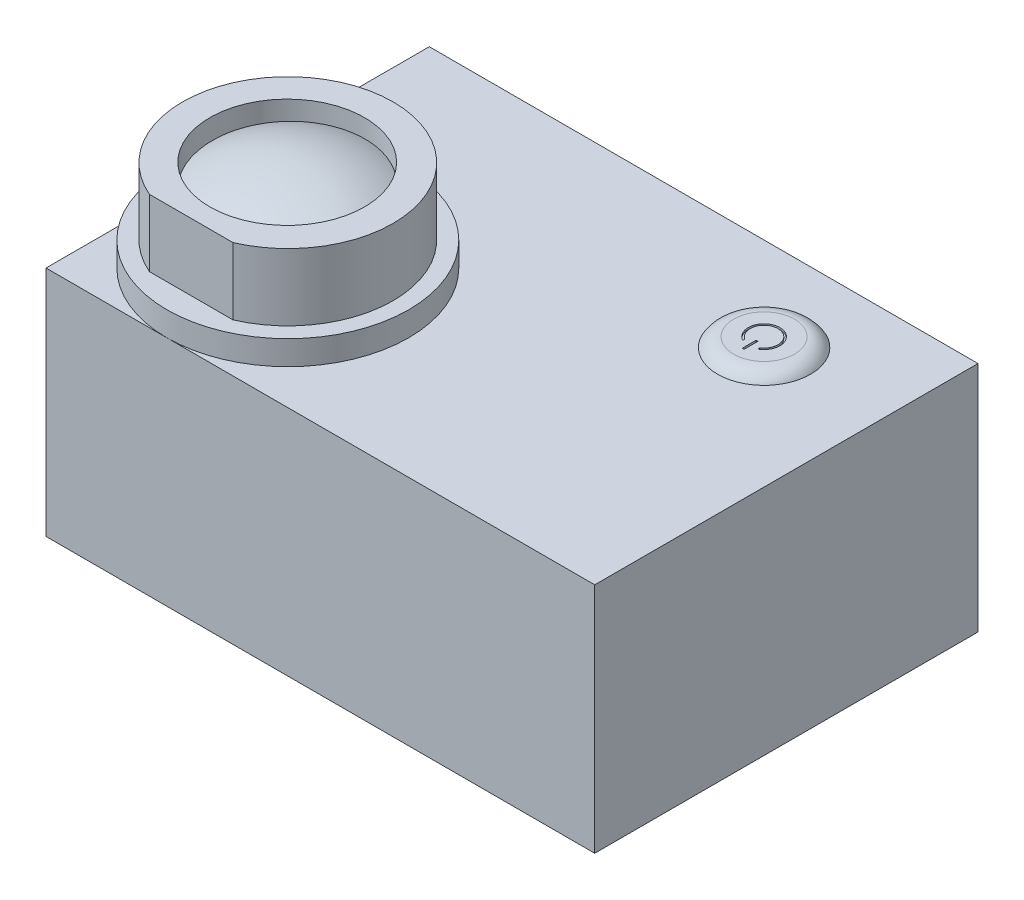
SolidWorks part; units mm, degrees
ref_plane "Alzado" through (0, 0, 0) normal (0, 0, 1) x (1, 0, 0)
ref_plane "Planta" through (0, 0, 0) normal (0, 1, 0) x (1, 0, 0)
ref_plane "Vista lateral" through (0, 0, 0) normal (1, 0, 0) x (0, 0, -1)
sketch "Croquis1" plane through (0, 0, 0) normal (0, 1, 0) x (1, 0, 0)
  line L1 (29.5, -20.605) -> (-29.5, -20.605)
  line L2 (29.5, -20.605) -> (29.5, 20.605)
  line L3 (29.5, 20.605) -> (-29.5, 20.605)
  line L4 (-29.5, -20.605) -> (-29.5, 20.605)
  line L5 (29.5, -20.605) -> (-29.5, 20.605) construction
  line L6 (29.5, 20.605) -> (-29.5, -20.605) construction
  point P0 (0, 0)
  dimension "D1" = 59
  dimension "D2" = 41.21
extrude "Saliente-Extruir1" add sketch "Croquis1" along normal blind 25
sketch "Croquis2" plane through (0, 25, 0) normal (0, 1, 0) x (1, 0, 0)
  line L0 (-29.5, 20.605) -> (-29.5, -20.605) construction
  line L1 (-29.5, -20.605) -> (29.5, -20.605) construction
  circle A0 centre (-16.5, -7.605) radius 13
  dimension "D1" = 26
extrude "Saliente-Extruir2" add sketch "Croquis2" along normal blind 9.81
sketch "Croquis4" plane through (0, 34.81, 0) normal (0, 1, 0) x (1, 0, 0)
  circle A0 centre (-16.5, -7.605) radius 11.32
  circle A1 centre (-16.5, -7.605) radius 13
extrude "Cortar-Extruir1" cut sketch "Croquis4" against normal blind 7.2
sketch "Croquis6" plane through (0, 34.81, 0) normal (0, 1, 0) x (1, 0, 0)
  line L1 (-12.0066, -17.995) -> (-20.9934, -17.995)
  arc A0 (-20.9934, -17.995) -> (-12.0066, -17.995) centre (-16.5, -7.605) ccw
  point P6 (-16.5, -17.995)
extrude "Cortar-Extruir2" cut sketch "Croquis6" against normal blind 7.2
sketch "Croquis7" plane through (0, 34.81, 0) normal (0, 1, 0) x (1, 0, 0)
  circle A0 centre (-16.5686, -7.6006) radius 8.32
extrude "Cortar-Extruir3" cut sketch "Croquis7" against normal blind 5
ref_plane "Plano1" through (-16.5, 0, 0) normal (-1, 0, 0) x (0, 0, 1)
sketch "Croquis9" plane through (-16.5, 0, 0) normal (-1, 0, 0) x (0, 0, 1)
  line L0 (15.9206, 32.31) -> (7.14, 32.31)
  line L1 (15.9206, 29.81) -> (15.9206, 34.81) construction
  line L2 (7.14, 32.31) -> (7.14, 34.81)
  line L3 (17.995, 34.81) -> (-3.715, 34.81) construction
  arc A0 (7.14, 34.81) -> (15.9206, 32.31) centre (7.14, 18.1403) cw
revolve "Revolución2" add sketch "Croquis9" angle 360 about L2
sketch "Croquis10" plane through (0, 25, 0) normal (0, 1, 0) x (1, 0, 0)
  circle A0 centre (16.5, 10.605) radius 5
extrude "Saliente-Extruir3" add sketch "Croquis10" along normal blind 1
fillet "Redondeo1" radius 2 1 edges at (16.5, 26, -5.605)
sketch "Croquis12" plane through (0, 26, 0) normal (0, 1, 0) x (1, 0, 0)
  line L0 (16.5, 10.605) -> (16.5, 9.855) construction
  line L1 (15.6938, 9.1945) -> (15.6938, 9.313)
  line L2 (16.55, 8.355) -> (16.45, 8.355)
  line L3 (16.6, 8.405) -> (16.6, 9.805)
  line L4 (16.55, 9.855) -> (16.45, 9.855)
  line L5 (16.4, 8.405) -> (16.4, 9.805)
  line L6 (17.3062, 9.1945) -> (17.3062, 9.313)
  arc A0 (17.3286, 9.3546) -> (15.6714, 9.3546) centre (16.5, 10.605) ccw
  arc A1 (17.3822, 9.1518) -> (15.6178, 9.1518) centre (16.5, 10.605) ccw
  arc A2 (15.6938, 9.1945) -> (15.6178, 9.1518) centre (15.6438, 9.1945) cw
  arc A3 (15.6714, 9.3546) -> (15.6938, 9.313) centre (15.6438, 9.313) cw
  arc A4 (17.3062, 9.1945) -> (17.3822, 9.1518) centre (17.3562, 9.1945) ccw
  arc A5 (17.3062, 9.313) -> (17.3286, 9.3546) centre (17.3562, 9.313) cw
  arc A6 (16.6, 8.405) -> (16.55, 8.355) centre (16.55, 8.405) cw
  arc A7 (16.4, 8.405) -> (16.45, 8.355) centre (16.45, 8.405) ccw
  arc A8 (16.55, 9.855) -> (16.6, 9.805) centre (16.55, 9.805) cw
  arc A9 (16.45, 9.855) -> (16.4, 9.805) centre (16.45, 9.805) ccw
  point P12 (15.6938, 9.1083)
  point P16 (15.6938, 9.3401)
  point P19 (17.3062, 9.1083)
  point P22 (17.3062, 9.3401)
  dimension "D1" = 0.05
  dimension "D2" = 0.05
  dimension "D3" = 0.05
extrude "Cortar-Extruir5" cut sketch "Croquis12" against normal blind 0.2
sketch "Croquis13" plane through (0, 0, -20.605) normal (0, 0, -1) x (-1, 0, 0)
  circle A0 centre (19, 13.3) radius 2.5
extrude "Cortar-Extruir6" cut sketch "Croquis13" against normal blind 5.2
thread "Rosca1" pitch 0.8 method extrude profile "Perfil de rosca1" start angle 0, offset 0, length 0, pitch 0.8, diameter 5
ref_plane "Plano2" through (-16.5, 13.3, -20.605) normal (0, -1, 0) x (1, 0, 0)
sketch "Perfil de rosca1" plane through (-16.5, 13.3, -20.605) normal (0, -1, 0) x (1, 0, 0)
  line L0 (0, 0) -> (0, 0.8) construction
  line L11 (0, 0) -> (0, 0.7)
  line L12 (0, 0.7) -> (-0.433, 0.45)
  line L13 (-0.433, 0.45) -> (-0.433, 0.25)
  line L15 (-0.433, 0.25) -> (0, 0)
  line L17 (-0.433, 0.35) -> (0, 0.35) construction
  point P2 (0, 0)
  dimension "Pitch" = 0.8
  dimension "Profile_Angle" = 60
  dimension "Profile_Land" = 0.2
  dimension "Profile_Height" = 0.433
sketch "Croquis16" plane through (-29.5, 0, 0) normal (-1, 0, 0) x (0, 0, 1)
  line L1 (-20.605, 25) -> (-20.605, 0) construction
  line L2 (-2.92, 17.66) -> (1.43, 17.66)
  line L4 (-2.3921, 20.4) -> (0.9021, 20.4)
  line L5 (1.93, 18.16) -> (1.93, 19.16)
  line L6 (1.93, 19.16) -> (1.3307, 20.1575)
  line L7 (-3.42, 18.16) -> (-3.42, 19.16)
  line L8 (-3.42, 19.16) -> (-2.8207, 20.1575)
  line L9 (-20.605, 25) -> (-20.605, 16.4)
  line L10 (-13.905, 16.9) -> (-13.905, 19.16)
  line L11 (-13.405, 16.4) -> (-6.445, 16.4)
  line L12 (-2.1027, 7.92) -> (-7.3176, 7.92)
  line L13 (-12.5324, 20.4) -> (-7.3176, 20.4)
  line L14 (-5.945, 16.9) -> (-5.945, 19.16)
  line L15 (-5.945, 19.16) -> (-6.9517, 20.2408)
  line L16 (-13.905, 19.16) -> (-12.8983, 20.2408)
  line L23 (-1.2302, 11.92) -> (-8.1902, 11.92)
  line L24 (-8.6902, 11.42) -> (-8.6902, 9.16)
  line L25 (-8.6902, 9.16) -> (-7.6834, 8.0792)
  line L26 (-0.7302, 9.16) -> (-1.7369, 8.0792)
  line L27 (-0.7302, 11.42) -> (-0.7302, 9.16)
  arc A0 (-13.405, 16.4) -> (-13.905, 16.9) centre (-13.405, 16.9) cw
  arc A1 (-5.945, 16.9) -> (-6.445, 16.4) centre (-6.445, 16.9) cw
  arc A2 (-2.92, 17.66) -> (-3.42, 18.16) centre (-2.92, 18.16) cw
  arc A3 (1.93, 18.16) -> (1.43, 17.66) centre (1.43, 18.16) cw
  arc A4 (-12.8983, 20.2408) -> (-12.5324, 20.4) centre (-12.5324, 19.9) cw
  arc A5 (-6.9517, 20.2408) -> (-7.3176, 20.4) centre (-7.3176, 19.9) ccw
  arc A6 (-2.3921, 20.4) -> (-2.8207, 20.1575) centre (-2.3921, 19.9) ccw
  arc A7 (1.3307, 20.1575) -> (0.9021, 20.4) centre (0.9021, 19.9) ccw
  arc A9 (-7.3176, 7.92) -> (-7.6834, 8.0792) centre (-7.3176, 8.42) cw
  arc A12 (-1.2302, 11.92) -> (-0.7302, 11.42) centre (-1.2302, 11.42) cw
  arc A13 (-8.6902, 11.42) -> (-8.1902, 11.92) centre (-8.1902, 11.42) cw
  arc A14 (-1.7369, 8.0792) -> (-2.1027, 7.92) centre (-2.1027, 8.42) cw
  point P22 (-13.905, 16.4)
  point P25 (-5.945, 16.4)
  point P61 (-7.3176, 7.92)
  dimension "D1" = 0.5
  dimension "D2" = 0.5
extrude "Cortar-Extruir8" cut sketch "Croquis16" against normal blind 4 contours L15 A5 L13 A4 L16 L10 A0 L11 A1 L14 | L6 A7 L4 A6 L8 L7 A2 L2 A3 L5 | A14 L26 L27 A12 L23 A13 L24 L25 A9 L12 region at (-29.5, 18.9725, -0.745) region at (-29.5, 18.3309, -9.925) region at (-29.5, 9.9891, -4.7102)
sketch "Croquis17" plane through (0, 0, -20.605) normal (0, 0, -1) x (-1, 0, 0)
  line L1 (14.5161, 17.0649) -> (24.005, 17.0649)
  line L2 (14.5161, 17.0649) -> (14.5161, 9.2098)
  line L3 (14.5161, 9.2098) -> (24.005, 9.2098)
  line L4 (24.005, 17.0649) -> (24.005, 9.2098)
extrude "Saliente-Extruir4" add sketch "Croquis17" against normal blind 10
